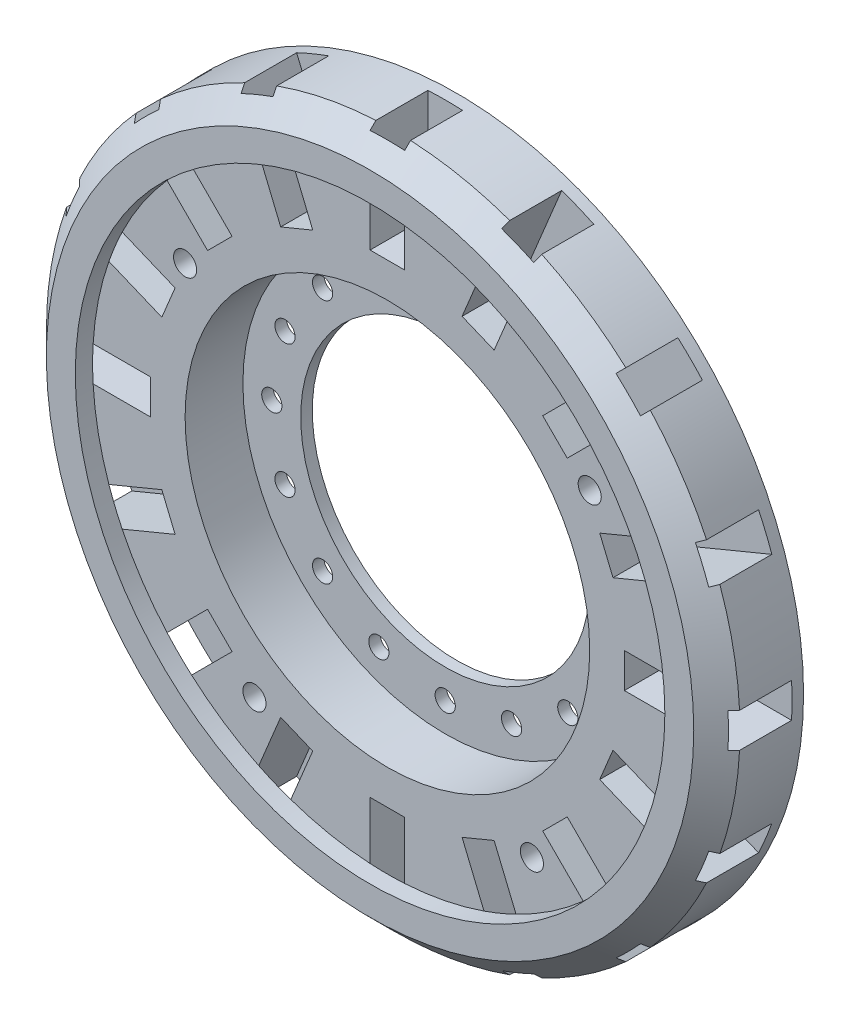
SolidWorks part; units mm, degrees
ref_plane "Front Plane" through (0, 0, 0) normal (0, 0, 1) x (1, 0, 0)
ref_plane "Top Plane" through (0, 0, 0) normal (0, 1, 0) x (1, 0, 0)
ref_plane "Right Plane" through (0, 0, 0) normal (1, 0, 0) x (0, 0, -1)
sketch "Sketch2" plane through (0, 0, 0) normal (0, 0, 1) x (1, 0, 0)
  circle A0 centre (0, 0) radius 35
  circle A1 centre (0, 0) radius 60
  dimension "D1" = 70
  dimension "D2" = 120
extrude "Boss-Extrude1" add sketch "Sketch2" along normal blind 15
sketch "Sketch3" plane through (0, 0, 15) normal (0, 0, 1) x (1, 0, 0)
  circle A0 centre (0, 0) radius 51
  dimension "D1" = 102
extrude "Cut-Extrude1" cut sketch "Sketch3" against normal blind 3
sketch "Sketch4" plane through (0, 0, 12) normal (0, 0, 1) x (1, 0, 0)
  line L0 (0, 51) -> (0, 0) construction
  line L1 (-3, 61) -> (3, 61)
  line L2 (-3, 61) -> (-3, 41)
  line L3 (-3, 41) -> (3, 41)
  line L4 (3, 61) -> (3, 41)
  line L5 (-3, 61) -> (3, 41) construction
  line L6 (-3, 41) -> (3, 61) construction
  circle A0 centre (0, 0) radius 51 construction
  circle A1 centre (0, 0) radius 51 construction
  point P0 (0, 51)
  point P12 (0, 26)
  point P13 (3, 18.6171)
  dimension "D1" = 6
  dimension "D2" = 20
extrude "Cut-Extrude2" cut sketch "Sketch4" against normal blind 10
pattern_circular "CirPattern1" count 16 over 360 about axis through (0, 0, 12) along (0, 0, 1) of "Cut-Extrude2"
chamfer "Chamfer1" distance 4 angle 45 1 edges at (60, 0, 15)
sketch "Sketch5" plane through (0, 0, 12) normal (0, 0, 1) x (1, 0, 0)
  circle A0 centre (25, -36) radius 2
  circle A1 centre (-23, -36) radius 2
  circle A2 centre (35, 24) radius 2
  circle A3 centre (-35, 23) radius 2
  dimension "D9" = 4
  dimension "D1" = 25
  dimension "D2" = 36
  dimension "D3" = 23
  dimension "D4" = 36
  dimension "D5" = 35
  dimension "D6" = 24
  dimension "D7" = 23
  dimension "D8" = 35
extrude "Cut-Extrude3" cut sketch "Sketch5" against normal through all
sketch "Sketch6" plane through (0, 0, 0) normal (0, 0, 1) x (1, 0, 0)
  line L1 (-35, 0) -> (0, 0) construction
  circle A1 centre (0, 0) radius 35 construction
  circle A3 centre (-30, 0) radius 1.75
  circle A4 centre (0, 0) radius 35
  circle A5 centre (0, 0) radius 25
  circle A6 centre (-27.7164, 11.4805) radius 1.75
  circle A7 centre (-21.2132, 21.2132) radius 1.75
  circle A8 centre (-11.4805, 27.7164) radius 1.75
  circle A9 centre (0, 30) radius 1.75
  circle A10 centre (11.4805, 27.7164) radius 1.75
  circle A11 centre (21.2132, 21.2132) radius 1.75
  circle A12 centre (27.7164, 11.4805) radius 1.75
  circle A13 centre (30, 0) radius 1.75
  circle A14 centre (27.7164, -11.4805) radius 1.75
  circle A15 centre (21.2132, -21.2132) radius 1.75
  circle A16 centre (11.4805, -27.7164) radius 1.75
  circle A17 centre (0, -30) radius 1.75
  circle A18 centre (-11.4805, -27.7164) radius 1.75
  circle A19 centre (-21.2132, -21.2132) radius 1.75
  circle A20 centre (-27.7164, -11.4805) radius 1.75
  point P43 (0, 0)
  dimension "D1" = 10
  dimension "D2" = 3.5
  dimension "D3" = 30
  dimension "D4" = 16
extrude "Boss-Extrude2" add sketch "Sketch6" along normal blind 2
